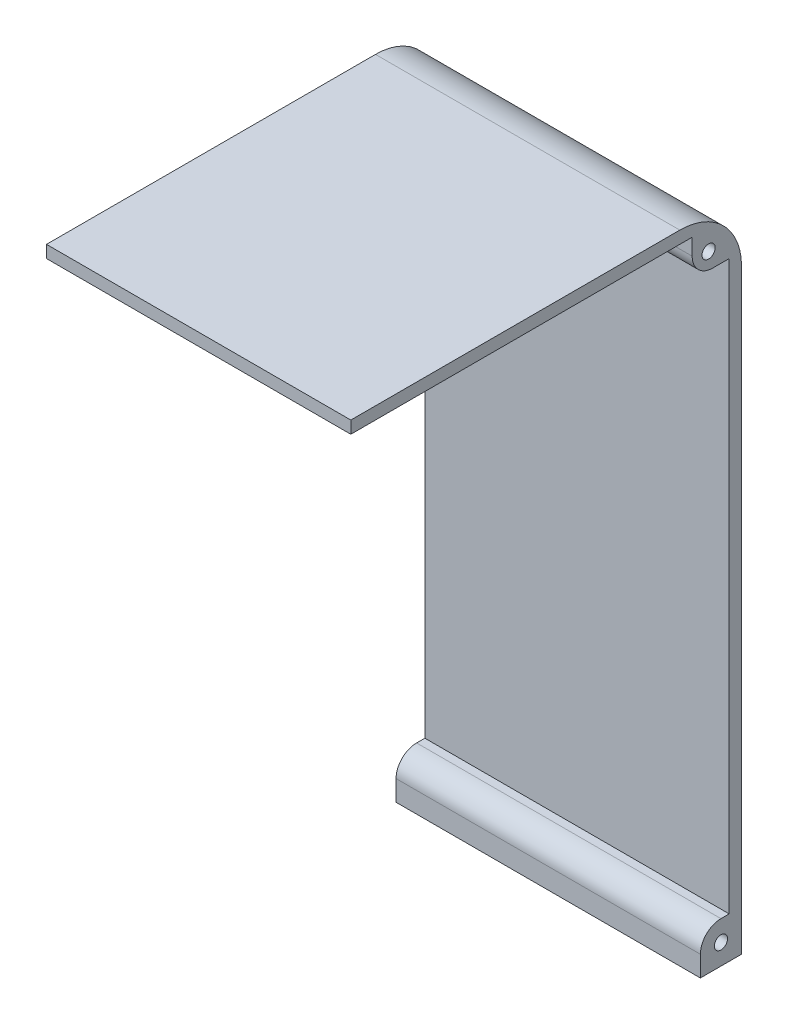
SolidWorks part; units mm, degrees
ref_plane "Front Plane" through (0, 0, 0) normal (0, 0, 1) x (1, 0, 0)
ref_plane "Top Plane" through (0, 0, 0) normal (0, 1, 0) x (1, 0, 0)
ref_plane "Right Plane" through (0, 0, 0) normal (1, 0, 0) x (0, 0, -1)
sketch "Sketch1" plane through (0, 0, 0) normal (1, 0, 0) x (0, 0, -1)
  line L1 (10, 0) -> (10, 160)
  line L2 (10, 160) -> (-85, 160)
  line L3 (-85, 160) -> (-85, 157)
  line L5 (7, 148) -> (7, 10)
  line L6 (-85, 157) -> (-2, 157)
  line L7 (-2, 157) -> (-2, 148)
  line L8 (-2, 148) -> (7, 148)
  line L10 (0, 0) -> (0, 10)
  line L11 (0, 10) -> (7, 10)
  line L12 (0, 0) -> (10, 0)
  circle A0 centre (2, 152) radius 1.6
  circle A1 centre (5, 5) radius 1.6
  dimension "D4" = 3.2
  dimension "D5" = 3.2
  dimension "D1" = 3
  dimension "D2" = 3
  dimension "D3" = 10
  dimension "D6" = 8
  dimension "D7" = 8
  dimension "D8" = 95
  dimension "D9" = 4
  dimension "D10" = 4
  dimension "D11" = 10
  dimension "D12" = 5
  dimension "D13" = 5
  dimension "D14" = 160
extrude "Boss-Extrude1" add sketch "Sketch1" along normal blind 74
fillet "Fillet1" radius 15 1 edges at (37, 160, -10)
fillet "Fillet2" radius 5 1 edges at (37, 10, 0)
fillet "Fillet3" radius 5 1 edges at (37, 148, 2)
